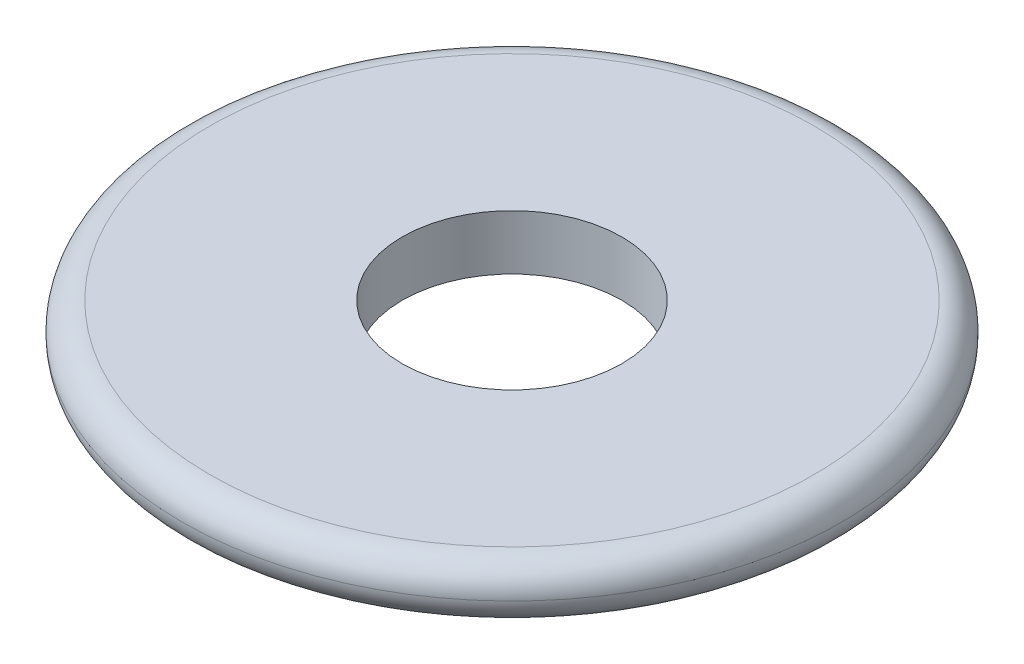
SolidWorks part; units mm, degrees
material "AISI 304"
ref_plane "Front" through (0, 0, 0) normal (0, 0, 1) x (1, 0, 0)
ref_plane "Top" through (0, 0, 0) normal (0, 1, 0) x (1, 0, 0)
ref_plane "Right" through (0, 0, 0) normal (1, 0, 0) x (0, 0, -1)
sketch "草图1" plane through (0, 0, 0) normal (0, 1, 0) x (1, 0, 0)
  circle A0 centre (0, 0) radius 4
  circle A1 centre (0, 0) radius 12
  dimension "垫圈内径" = 8
  dimension "垫圈外径" = 24
extrude "凸台-拉伸1" add sketch "草图1" along normal mid plane 2
fillet "圆角1" radius 1 2 edges at (0, -1, 12) (0, 1, 12)
